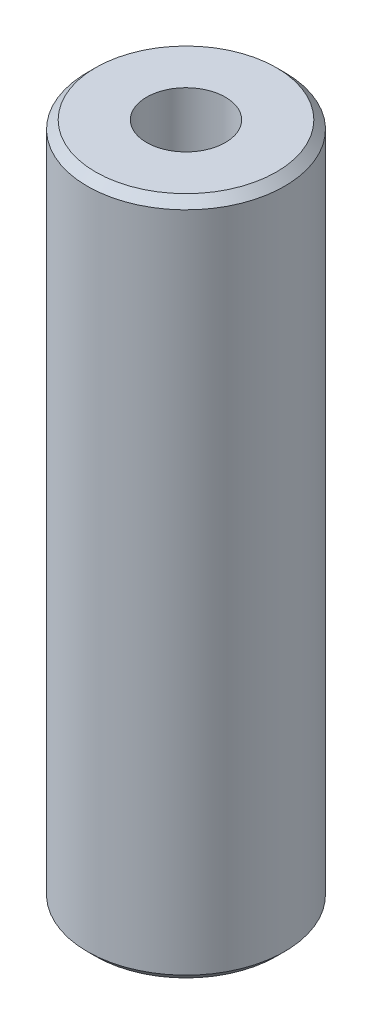
SolidWorks part; units mm, degrees
ref_plane "Front Plane" through (0, 0, 0) normal (0, 0, 1) x (1, 0, 0)
ref_plane "Top Plane" through (0, 0, 0) normal (0, 1, 0) x (1, 0, 0)
ref_plane "Right Plane" through (0, 0, 0) normal (1, 0, 0) x (0, 0, -1)
sketch "Sketch1" plane through (0, 0, 0) normal (0, 1, 0) x (1, 0, 0)
  circle A0 centre (0, 0) radius 57.5
  dimension "SHAFT_OD" = 115
extrude "Boss-Extrude1" add sketch "Sketch1" along normal blind 395.9403
sketch "Sketch2" plane through (0, 0, 0) normal (0, 1, 0) x (1, 0, 0)
  circle A0 centre (0, 0) radius 22.9558
  dimension "BORE_D" = 45.9116
extrude "Cut-Extrude1" cut sketch "Sketch2" along normal through all
chamfer "Chamfer1" distance 4.7963 angle 45 2 edges at (0, 395.9403, 57.5) (0, 0, 57.5)
